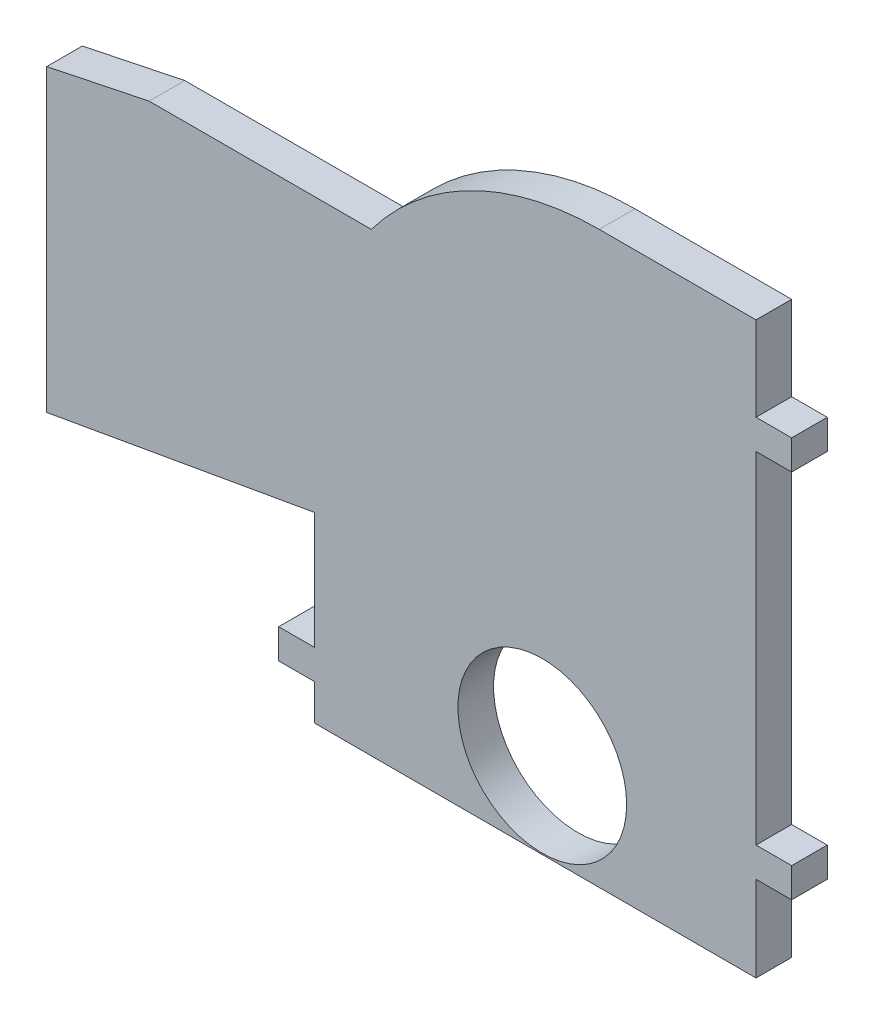
SolidWorks part; units mm, degrees
material "Balsa"
ref_plane "Front Plane" through (0, 0, 0) normal (0, 0, 1) x (1, 0, 0)
ref_plane "Top Plane" through (0, 0, 0) normal (0, 1, 0) x (1, 0, 0)
ref_plane "Right Plane" through (0, 0, 0) normal (1, 0, 0) x (0, 0, -1)
sketch "Sketch1" plane through (0, 0, 0) normal (0, 0, 1) x (1, 0, 0)
  line L0 (0, -1000.1535) -> (0, 48999.8465) construction
  line L1 (-7.62, 16.51) -> (-17.5195, 16.51)
  line L2 (-1000, 0) -> (49000, 0) construction
  line L3 (9.525, 16.51) -> (11.1125, 16.51)
  line L4 (2.54, 21.59) -> (9.525, 21.59)
  line L5 (-10.16, 8.89) -> (-10.16, -3.81)
  line L6 (-10.16, -3.81) -> (9.525, -3.81)
  line L7 (9.525, 21.59) -> (9.525, -3.81)
  line L8 (-11.7475, -2.2098) -> (-10.16, -2.2098)
  line L9 (-11.7475, -2.2098) -> (-11.7475, -0.889)
  line L10 (-11.7475, -0.889) -> (-10.16, -0.889)
  line L11 (-10.16, -2.2098) -> (-10.16, -0.889)
  line L12 (9.525, 0) -> (11.1125, 0)
  line L13 (9.525, 0) -> (9.525, 1.3208)
  line L14 (9.525, 1.3208) -> (11.1125, 1.3208)
  line L15 (11.1125, 0) -> (11.1125, 1.3208)
  line L16 (9.525, 16.51) -> (9.525, 17.8308)
  line L17 (9.525, 17.8308) -> (11.1125, 17.8308)
  line L18 (11.1125, 16.51) -> (11.1125, 17.8308)
  line L20 (-22.0849, 2.212) -> (-10.16, 4.318)
  line L21 (-22.0849, 4.699) -> (-22.0849, 2.212)
  line L22 (-22.0849, 13.081) -> (-22.0849, 4.699)
  line L26 (-17.5195, 16.51) -> (-22.0849, 15.5612)
  line L27 (-22.0849, 13.081) -> (-22.0849, 15.5612)
  circle A0 centre (0, 0) radius 3.7592
  arc A3 (2.54, 21.59) -> (-10.16, 8.89) centre (2.54, 8.89) ccw
  dimension "D1" = 7.5184
  dimension "D4" = 3.81
  dimension "D3" = 7.3595
  dimension "D5" = 0.9488
  dimension "D9" = 12.7
  dimension "D10" = 1.5875
  dimension "D2" = 25.4
  dimension "D6" = 9.525
  dimension "D7" = 2.106
  dimension "D8" = 19.685
  dimension "D11" = 5.207
  dimension "D12" = 1.3208
  dimension "D13" = 1.3208
  dimension "D14" = 1.5875
  dimension "D15" = 2
extrude "Boss-Extrude1" add sketch "Sketch1" along normal blind 1.5875 contours L4 A3 L5 L6 L7 A0 | L10 L9 L8 L5 | L3 L18 L17 L7 | L12 L15 L14 L7 | A3 L1 L20 L5 | L20 region at (-15.9616, 9.9708, 0) region at (0.225, 9.0166, 0) region at (10.3187, 17.1704, 0) region at (-10.9538, -1.5494, 0) region at (10.3187, 0.6604, 0)
move or copy body "Body-Move/Copy1" [suppressed] bodies to move or copy 101
